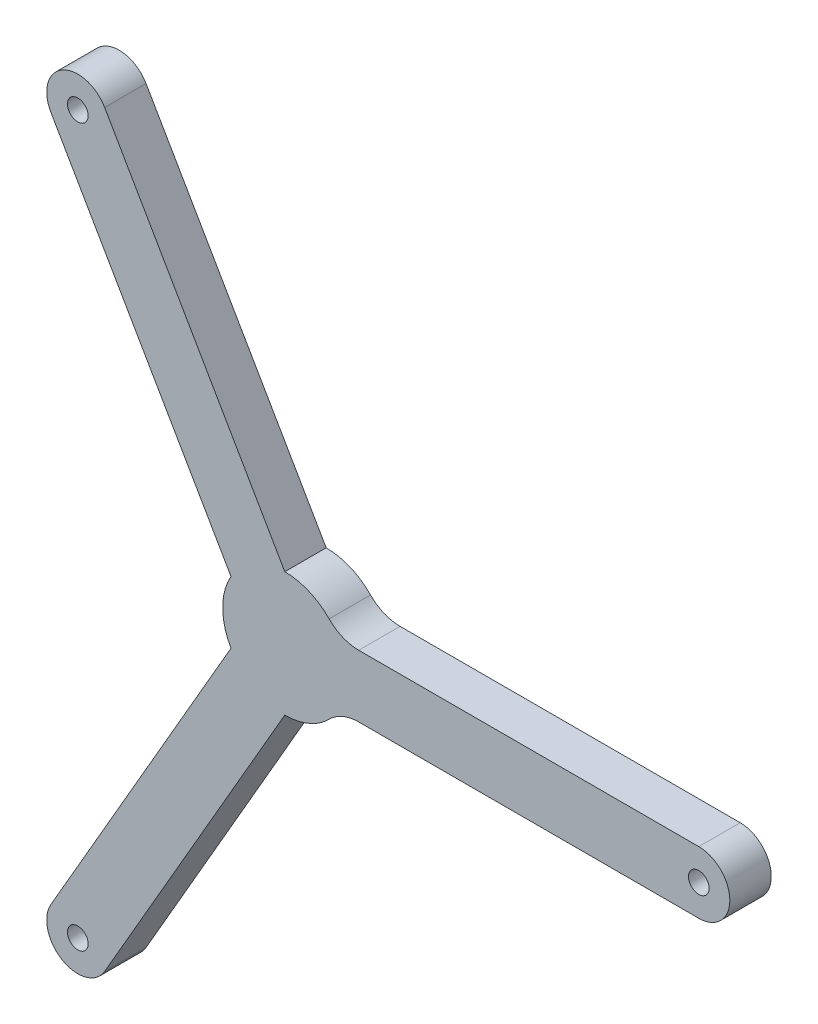
SolidWorks part; units mm, degrees
ref_plane "Front Plane" through (0, 0, 0) normal (0, 0, 1) x (1, 0, 0)
ref_plane "Top Plane" through (0, 0, 0) normal (0, 1, 0) x (1, 0, 0)
ref_plane "Right Plane" through (0, 0, 0) normal (1, 0, 0) x (0, 0, -1)
sketch "Sketch1" plane through (0, 0, 0) normal (0, 0, 1) x (1, 0, 0)
  line L0 (0, 0) -> (100, 0) construction
  line L1 (0, 7.5) -> (100, 7.5)
  line L2 (100, -7.5) -> (12.9904, -7.5)
  circle A0 centre (100, 0) radius 7.5
  circle A1 centre (0, 0) radius 15
  circle A2 centre (100, 0) radius 2.5
  point P11 (100, 0)
  dimension "pin diameter" = 5
  dimension "D1" = 15
  dimension "D2" = 30
  dimension "pin distance" = 100
extrude "Boss-Extrude1" add sketch "Sketch1" along normal blind 10 contours A1 | A1 L0 A0 L1 | L0 A1 L2 A0 | A0 A2 region at (54.2447, 3.8074, 0) region at (54.2447, -3.8074, 0) region at (14.0791, -3.7725, 0) region at (94.8467, 5.1533, 0)
fillet "Fillet1" radius 10 2 edges at (12.9904, 7.5, 5) (12.9904, -7.5, 5)
pattern_circular "CirPattern1" count 3 over 360 about axis through (0, 0, 10) along (0, 0, -1) of "Boss-Extrude1"
ref_axis "Axis1" through (100, 0, 10) along (0, 0, -1)
ref_axis "Axis2" through (-50, 86.6025, 10) along (0, 0, -1)
ref_axis "Axis3" through (-50, -86.6025, 10) along (0, 0, -1)
ref_axis "Axis4" through (0, 0, 0) along (0, 0, 1)
equation "\"D1@Sketch1\"= \"pin diameter@Sketch1\" + 1"
